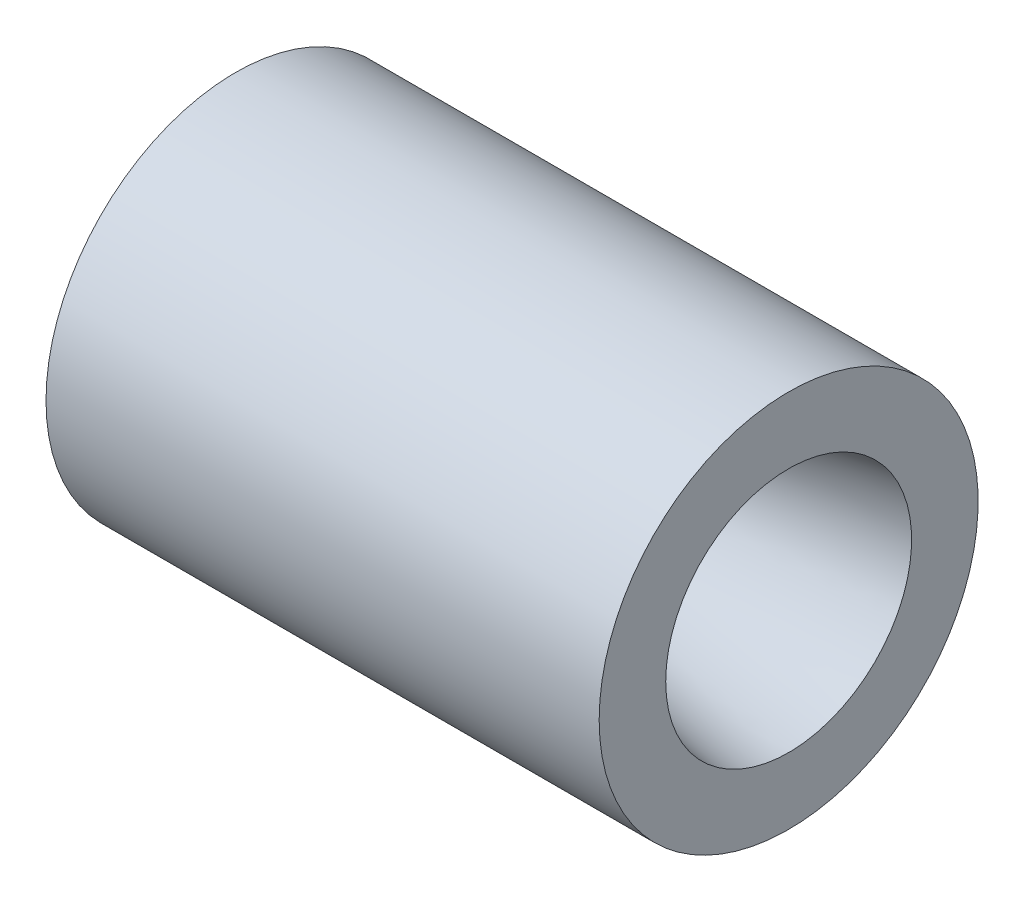
SolidWorks part; units mm, degrees
ref_plane "Front Plane" through (0, 0, 0) normal (0, 0, 1) x (1, 0, 0)
ref_plane "Top Plane" through (0, 0, 0) normal (0, 1, 0) x (1, 0, 0)
ref_plane "Right Plane" through (0, 0, 0) normal (1, 0, 0) x (0, 0, -1)
sketch "Sketch1" plane through (0, 0, 0) normal (0, 0, 1) x (1, 0, 0)
  line L0 (0, 0) -> (176.8872, 0) construction
  line L1 (0, 41.295) -> (27.5254, 41.295) construction
  line L2 (54.4274, 15.285) -> (96.5346, 15.285) construction
  line L3 (42.9453, 29.8255) -> (62.8124, 18.3553)
  line L7 (0, 41.295) -> (0, 50.82)
  line L8 (0, 50.82) -> (148.34, 50.82)
  line L9 (148.34, 50.82) -> (148.34, 32.975)
  line L11 (75.9338, 15.5588) -> (94.1128, 21.868) construction
  line L13 (148.34, 32.975) -> (123.4215, 29.4729) construction
  arc A0 (0, 41.295) -> (42.9453, 29.8255) centre (0.1403, -44.3149) cw
  arc A1 (74.13, 15.285) -> (62.8124, 18.3553) centre (74.2724, 38.2046) cw
  arc A2 (74.13, 15.285) -> (75.9338, 15.5588) centre (74.1663, 21.1249) ccw
  spline S0 degree 3 poles (75.9338, 15.5588) (97.1242, 22.9132) (126.0123, 29.837) (148.34, 32.975) knots 0 0 0 0 1 1 1 1
  dimension "D4" = 22.92
  dimension "D5" = 74.13
  dimension "D7" = 5.84
  dimension "D11" = 9.525
  dimension "D6" = 30
  dimension "D3" = 85.61
  dimension "D9" = 74.21
  dimension "D1" = 41.295
  dimension "D2" = 15.285
  dimension "D8" = 19.14
  dimension "D10" = 32.975
  dimension "D12" = 8
revolve "Revolve1" add sketch "Sketch1" angle 360 about L0
